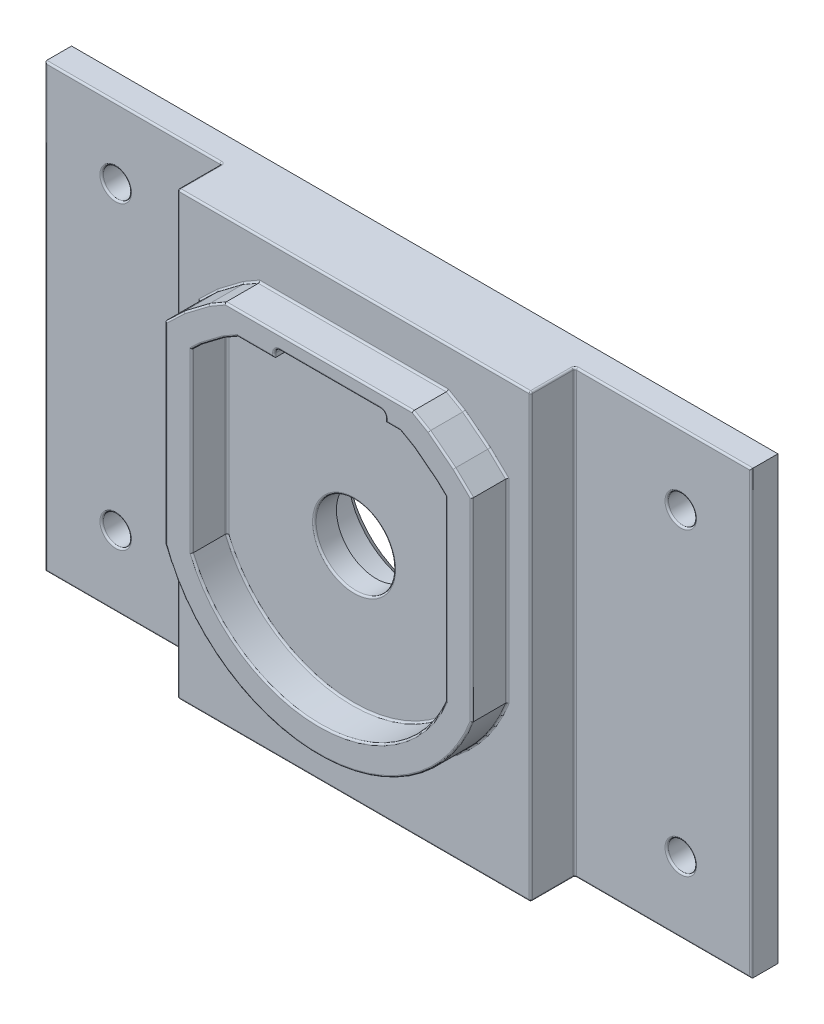
SolidWorks part; units mm, degrees
ref_plane "Front Plane" through (0, 0, 0) normal (0, 0, 1) x (1, 0, 0)
ref_plane "Top Plane" through (0, 0, 0) normal (0, 1, 0) x (1, 0, 0)
ref_plane "Right Plane" through (0, 0, 0) normal (1, 0, 0) x (0, 0, -1)
sketch "Sketch1" plane through (0, 0, 0) normal (0, 0, 1) x (1, 0, 0)
  line L1 (-40, -25) -> (40, -25)
  line L2 (-40, -25) -> (-40, 25)
  line L3 (-40, 25) -> (40, 25)
  line L4 (40, -25) -> (40, 25)
  line L5 (-40, -25) -> (40, 25) construction
  line L6 (-40, 25) -> (40, -25) construction
  point P0 (0, 0)
  point P5 (-50, 21.7337)
  dimension "D1" = 80
  dimension "D2" = 50
extrude "Boss-Extrude1" add sketch "Sketch1" along normal blind 3
sketch "Sketch6" plane through (0, 0, 3) normal (0, 0, 1) x (1, 0, 0)
  line L0 (40, 25) -> (-40, 25) construction
  line L1 (20, -25) -> (-20, -25)
  line L2 (20, -25) -> (20, 25)
  line L3 (20, 25) -> (-20, 25)
  line L4 (-20, -25) -> (-20, 25)
  line L5 (20, -25) -> (-20, 25) construction
  line L6 (20, 25) -> (-20, -25) construction
  point P0 (0, 0)
  dimension "D1" = 40
extrude "Boss-Extrude3" add sketch "Sketch6" along normal blind 5
sketch "Sketch3" plane through (0, 0, 8) normal (0, 0, 1) x (1, 0, 0)
  line L0 (-14.3953, -5.9991) -> (-14.3953, 14.0234)
  line L1 (-14.3953, 14.0234) -> (-13.3642, 15.0075)
  line L2 (-10.8024, 16.9451) -> (-13.3642, 15.0075)
  line L3 (-10.8024, 16.9451) -> (-9.2024, 17.8657)
  line L4 (-9.2024, 17.8657) -> (-5.0253, 17.8657)
  line L5 (-5.0253, 17.8657) -> (-5.0253, 18.3079)
  line L6 (-4.4301, 18.9031) -> (6.9701, 18.9031)
  line L7 (7.5653, 18.3079) -> (7.5653, 17.8657)
  line L8 (7.5653, 17.8657) -> (9.2024, 17.8657)
  line L9 (9.2024, 17.8657) -> (10.8031, 16.9447)
  line L10 (10.8031, 16.9447) -> (13.371, 14.9429)
  line L11 (13.371, 14.9429) -> (14.3516, 14.0055)
  line L12 (14.3516, 14.0055) -> (14.3516, -6.1027)
  line L13 (-17.3953, -6.5718) -> (-17.3953, 15.3072)
  line L14 (-17.3953, 15.3072) -> (-15.3111, 17.2964)
  line L15 (-12.4619, 19.4514) -> (-15.3111, 17.2964)
  line L16 (-12.4619, 19.4514) -> (-10.6394, 20.5)
  line L17 (10.6394, 20.5) -> (12.4815, 19.4401)
  line L18 (12.4815, 19.4401) -> (15.3347, 17.2159)
  line L19 (15.3347, 17.2159) -> (17.3516, 15.288)
  line L20 (17.3516, 15.288) -> (17.3516, -6.6862)
  line L21 (-10.6394, 20.5) -> (10.6394, 20.5)
  arc A0 (-5.0253, 18.3079) -> (-4.4301, 18.9031) centre (-4.4301, 18.3079) cw
  arc A1 (6.9701, 18.9031) -> (7.5653, 18.3079) centre (6.9701, 18.3079) cw
  arc A2 (-14.3953, -5.9991) -> (14.3516, -6.1027) centre (0, 0) ccw
  arc A3 (-17.3953, -6.5718) -> (17.3516, -6.6862) centre (0, 0) ccw
  point P30 (0, 0)
  point P31 (0, 0)
  point P32 (0, 0)
  point P33 (0, 0)
  point P34 (0, 0)
  point P35 (0, 0)
  point P36 (4.7447, -1.5332)
  point P38 (0.4567, 0)
  dimension "D1" = 15.5953
  dimension "D9" = 0.5952
  dimension "D16" = 0.5952
  dimension "D2" = 5.9991
  dimension "D3" = 20.0224
  dimension "D4" = 20.1082
  dimension "D5" = 1.3566
  dimension "D6" = 3.256
  dimension "D7" = 1.8467
  dimension "D8" = 1.6371
  dimension "D10" = 0.4422
  dimension "D11" = 11.4002
  dimension "D12" = 1.4253
  dimension "D13" = 3.212
  dimension "D14" = 1.846
  dimension "D15" = 4.1771
  dimension "D17" = 0.4422
  dimension "D18" = 0.9373
  dimension "D19" = 2.0018
  dimension "D20" = 0.921
  dimension "D21" = 0.9206
  dimension "D22" = 1.9376
  dimension "D23" = 2.8811
  dimension "D24" = 2.7902
  dimension "D25" = 3.6176
  dimension "D26" = 2.1253
  dimension "D27" = 3.5724
  dimension "D28" = 2.1026
  dimension "D29" = 21.2787
  dimension "D30" = 1.5969
  dimension "D31" = 21.879
  dimension "D32" = 21.9742
extrude "Boss-Extrude2" add sketch "Sketch3" along normal blind 4
sketch "Sketch4" plane through (0, 0, 8) normal (0, 0, 1) x (1, 0, 0)
  line L1 (3.6373, 0) -> (1.8187, 3.15) construction
  line L2 (1.8187, 3.15) -> (-1.8187, 3.15) construction
  line L3 (-1.8187, 3.15) -> (-3.6373, 0) construction
  line L4 (-3.6373, 0) -> (-1.8187, -3.15) construction
  line L5 (-1.8187, -3.15) -> (1.8187, -3.15) construction
  line L6 (1.8187, -3.15) -> (3.6373, 0) construction
  circle A0 centre (0, 0) radius 3.15 construction
  circle A1 centre (0, 0) radius 4.5
  dimension "D2" = 9
  dimension "D1" = 6.3
extrude "Cut-Extrude2" cut sketch "Sketch4" against normal up to next
sketch "Sketch7" plane through (0, 0, 0) normal (0, 0, -1) x (-1, 0, 0)
  circle A0 centre (0, 0) radius 7.75
  dimension "D1" = 15.5
extrude "Cut-Extrude3" cut sketch "Sketch7" against normal blind 5.5
sketch "Sketch9" plane through (0, 0, 3) normal (0, 0, 1) x (1, 0, 0)
  line L0 (40, 25) -> (20, 25) construction
  line L1 (-32, 17) -> (32, 17) construction
  line L2 (-32, 17) -> (-32, -17) construction
  line L3 (-32, -17) -> (32, -17) construction
  line L4 (32, 17) -> (32, -17) construction
  line L5 (40, -25) -> (40, 25) construction
  circle A0 centre (-32, 17) radius 1.5875
  circle A1 centre (-32, -17) radius 1.5875
  circle A2 centre (32, -17) radius 1.5875
  circle A3 centre (32, 17) radius 1.5875
  point P2 (0, -17)
  point P6 (-32.446, -15.8824)
  point P8 (0, 0)
  point P11 (31.1686, -15.2862)
  point P12 (-31.3389, -15.8824)
  point P14 (32, 0)
  dimension "D1" = 3.175
  dimension "D2" = 8
  dimension "D3" = 8
extrude "Cut-Extrude4" cut sketch "Sketch9" against normal up to next
fillet "Fillet1" radius 0.2 73 edges at (-30, 25, 3) (-30, -25, 3) (30, -25, 3) (30, 25, 3) (-20, 25, 5.5) (-20, -25, 5.5) (-20, 0, 3) (20, -25, 5.5) (20, 25, 5.5) (20, 0, 3) (16.3432, 16.252, 8) (13.9081, 18.328, 8) (11.5605, 19.97, 8) (0, 20.5, 8) (-11.5506, 19.9757, 8) (-13.8865, 18.3739, 8) (-16.3532, 16.3018, 8) (-17.3953, 4.3677, 8) (-0.0612, -18.5952, 8) (17.3516, 4.3009, 8) (0, 25, 8) (20, 0, 8) (0, -25, 8) (-20, 0, 8) (13.8613, 14.4742, 12) (12.087, 15.9438, 12) (10.0027, 17.4052, 12) (8.3838, 17.8657, 12) (7.5653, 18.0868, 12) (7.391, 18.7288, 12) (1.27, 18.9031, 12) (-4.851, 18.7288, 12) (-5.0253, 18.0868, 12) (-7.1138, 17.8657, 12) (-10.0024, 17.4054, 12) (-12.0833, 15.9763, 12) (-13.8797, 14.5154, 12) (-14.3953, 4.0122, 12) (-0.0562, -15.5952, 12) (14.3516, 3.9514, 12) (-17.3953, 4.3677, 12) (-16.3532, 16.3018, 12) (-13.8865, 18.3739, 12) (-11.5506, 19.9757, 12) (0, 20.5, 12) (11.5605, 19.97, 12) (13.9081, 18.328, 12) (16.3432, 16.252, 12) (17.3516, 4.3009, 12) (-0.0612, -18.5952, 12) (-14.3953, 4.0122, 8) (-13.8797, 14.5154, 8) (-12.0833, 15.9763, 8) (-10.0024, 17.4054, 8) (-7.1138, 17.8657, 8) (-5.0253, 18.0868, 8) (-4.851, 18.7288, 8) (1.27, 18.9031, 8) (7.391, 18.7288, 8) (7.5653, 18.0868, 8) (8.3838, 17.8657, 8) (10.0027, 17.4052, 8) (12.087, 15.9438, 8) (13.8613, 14.4742, 8) (14.3516, 3.9514, 8) (-0.0562, -15.5952, 8) (4.5, 0, 8) (40, 0, 3) (33.5875, -17, 3) (33.5875, 17, 3) (-40, 0, 3) (-30.4125, 17, 3) (-30.4125, -17, 3)
chamfer "Chamfer1" distance 1 angle 45 1 edges at (-7.75, 0, 0)
